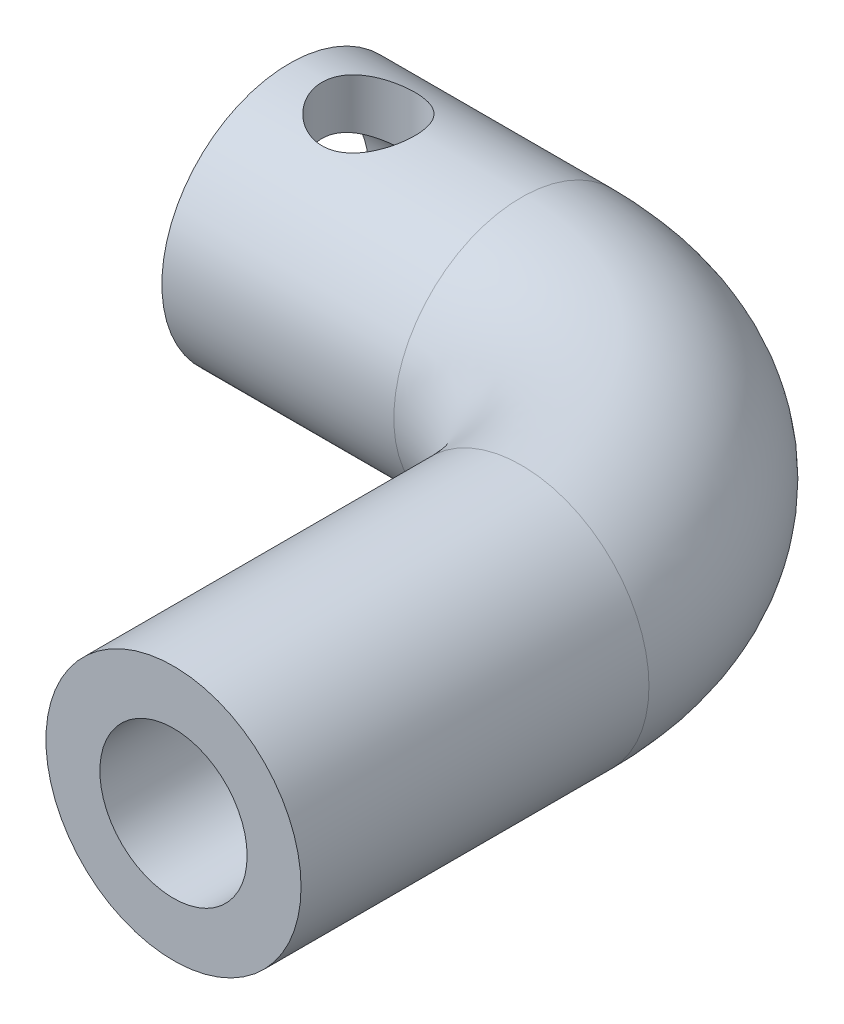
SolidWorks part; units mm, degrees
ref_plane "Front Plane" through (0, 0, 0) normal (0, 0, 1) x (1, 0, 0)
ref_plane "Top Plane" through (0, 0, 0) normal (0, 1, 0) x (1, 0, 0)
ref_plane "Right Plane" through (0, 0, 0) normal (1, 0, 0) x (0, 0, -1)
sketch "PROFILE" plane through (0, 0, 0) normal (0, 1, 0) x (1, 0, 0)
  line L0 (2.5, -10) -> (2.5, -25)
  line L1 (-7.5, 0) -> (-17.5, 0)
  arc A0 (2.5, -10) -> (-7.5, 0) centre (-7.5, -10) ccw
  dimension "D1" = 10
  dimension "D2" = 10
  dimension "D3" = 15
ref_plane "Plane1" through (0, 0, 25) normal (0, 0, 1) x (1, 0, 0)
sketch "Sketch4" plane through (0, 0, 25) normal (0, 0, 1) x (1, 0, 0)
  line L0 (2.5, 0) -> (-7.5, 0) construction
  circle A0 centre (2.5, 0) radius 5.5
  dimension "D1" = 11
sweep "Sweep2" add profiles "Sketch4" path "PROFILE"
sketch "Sketch6" plane through (0, 0, 25) normal (0, 0, 1) x (1, 0, 0)
  circle A0 centre (2.5, 0) radius 3.175
extrude "HOLE_SHAFT" cut sketch "Sketch6" against normal blind 10
sketch "Sketch7" plane through (-17.5, 0, 0) normal (-1, 0, 0) x (0, 0, 1)
  circle A0 centre (0, 0) radius 3.4
extrude "HOLE_POT" cut sketch "Sketch7" against normal blind 10
sketch "Sketch8" plane through (0, 0, 0) normal (0, 1, 0) x (1, 0, 0)
  line L0 (-7.5, 0) -> (-17.5, 0) construction
  circle A0 centre (-14.0963, 0) radius 2
extrude "HOLE_INSERT" cut sketch "Sketch8" along normal through all
ref_axis "Axis1" through (-18.775, 0, 0) along (1, 0, 0)
ref_plane "Plane2" through (0, 0, 0) normal (0, 1, 0) x (1, 0, 0)
sketch "Sketch11" plane through (-7.5, 0, 0) normal (-1, 0, 0) x (0, 0, 1)
  line L0 (15.4275, 0) -> (-15.4275, 0) construction
  line L1 (1.6456, -2.8793) -> (-2.4561, 2.4663)
  line L2 (1.6456, -2.8793) -> (2.439, -2.2705)
  line L3 (2.439, -2.2705) -> (-1.6628, 3.075)
  line L4 (-2.4561, 2.4663) -> (-1.6628, 3.075)
  line L5 (-3.369, 0.5) -> (3.369, -0.5) construction
  line L6 (-3.369, -0.5) -> (3.369, 0.5) construction
  point P0 (0, 0)
  dimension "D1" = 1
  dimension "D2" = 52.5
extrude "SLOT_BOSS" add sketch "Sketch11" along normal blind 1
